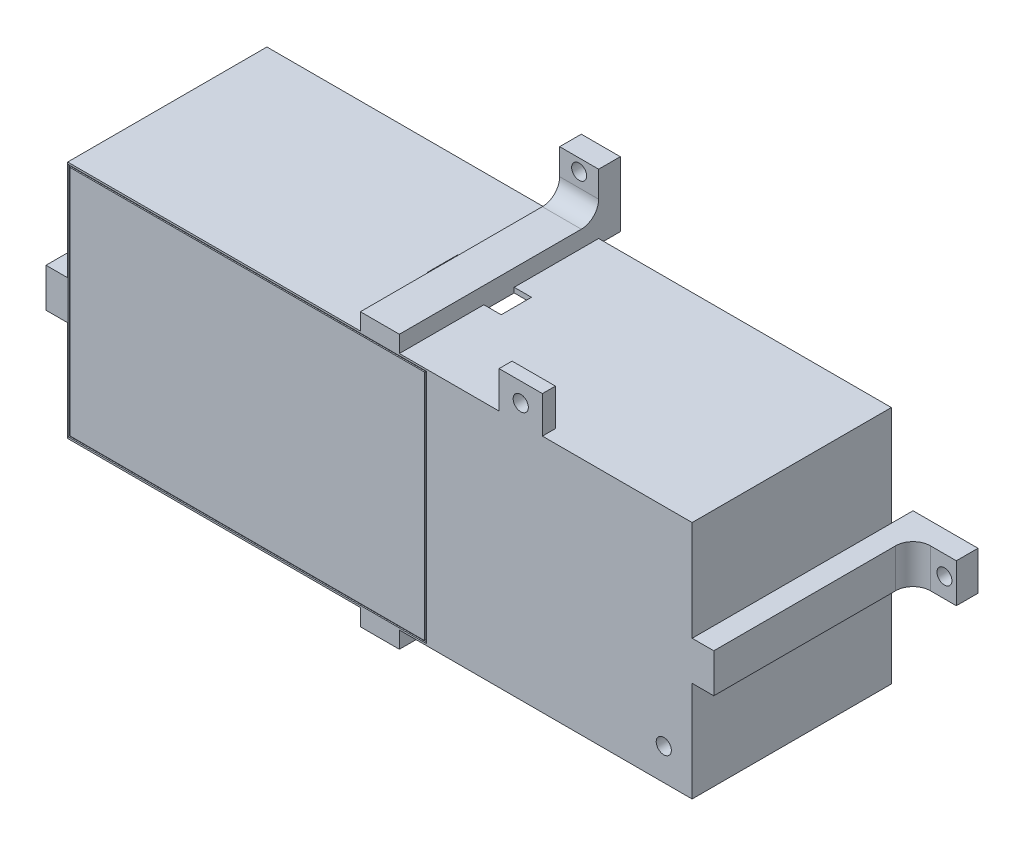
SolidWorks part; units mm, degrees
ref_plane "Front Plane" through (0, 0, 0) normal (0, 0, 1) x (1, 0, 0)
ref_plane "Top Plane" through (0, 0, 0) normal (0, 1, 0) x (1, 0, 0)
ref_plane "Right Plane" through (0, 0, 0) normal (1, 0, 0) x (0, 0, -1)
sketch "Sketch2" plane through (0, 0, 0) normal (0, 0, 1) x (1, 0, 0)
  line L0 (-68.085, -22.5) -> (68.085, 22.5) construction
  line L1 (-68.085, 22.5) -> (68.085, 22.5) construction
  line L2 (-68.085, 22.5) -> (-68.085, -22.5) construction
  line L3 (-68.085, -22.5) -> (68.085, -22.5) construction
  line L4 (68.085, 22.5) -> (68.085, -22.5) construction
  line L5 (-72.085, 26.5) -> (72.085, 26.5) construction
  line L6 (72.085, 26.5) -> (72.085, -26.5) construction
  line L7 (-72.085, -26.5) -> (72.085, -26.5) construction
  line L8 (-72.085, 26.5) -> (-72.085, -26.5) construction
  line L9 (0, 0) -> (-100, 0) construction
  line L10 (-77.085, 4.5) -> (-72.085, 4.5)
  line L11 (-77.085, 4.5) -> (-77.085, -4.5)
  line L12 (-77.085, -4.5) -> (-72.085, -4.5)
  line L13 (-72.085, 4.5) -> (-72.085, -4.5)
  line L14 (-4.5, 31.5) -> (4.5, 31.5)
  line L15 (-4.5, 31.5) -> (-4.5, 26.5)
  line L16 (-4.5, 26.5) -> (4.5, 26.5)
  line L17 (4.5, 31.5) -> (4.5, 26.5)
  line L18 (0, 0) -> (0, 108.7377) construction
  line L19 (-77.085, 4.5) -> (-72.085, -4.5) construction
  line L20 (-4.5, 26.5) -> (4.5, 31.5) construction
  line L21 (77.085, -4.5) -> (72.085, -4.5)
  line L22 (77.085, 4.5) -> (77.085, -4.5)
  line L23 (72.085, 4.5) -> (72.085, -4.5)
  line L24 (77.085, 4.5) -> (72.085, 4.5)
  line L25 (-4.5, -26.5) -> (4.5, -26.5)
  line L26 (-4.5, -31.5) -> (-4.5, -26.5)
  line L27 (-4.5, -31.5) -> (4.5, -31.5)
  line L28 (4.5, -31.5) -> (4.5, -26.5)
  point P4 (0, 0)
  point P23 (-74.585, 0)
  point P25 (0, 29)
  dimension "D1" = 45
  dimension "D2" = 136.17
  dimension "D4" = 5
  dimension "D5" = 9
  dimension "D6" = 5
  dimension "D7" = 9
  dimension "D3" = 4
extrude "Boss-Extrude1" add sketch "Sketch2" along normal blind 48
sketch "Sketch3" plane through (0, 0, 48) normal (0, 0, 1) x (1, 0, 0)
  line L0 (-82.5, 27.64) -> (82.5, -27.64) construction
  line L1 (-82.5, 27.64) -> (82.5, 27.64)
  line L2 (-82.5, 27.64) -> (-82.5, -27.64)
  line L3 (-82.5, -27.64) -> (82.5, -27.64)
  line L4 (82.5, 27.64) -> (82.5, -27.64)
  point P4 (0, 0)
  dimension "D1" = 165
  dimension "D2" = 55.28
extrude "Boss-Extrude2" add sketch "Sketch3" along normal blind 3
sketch "Sketch4" plane through (0, 0, 48) normal (0, 0, 1) x (1, 0, 0)
  line L0 (-4.5, 27.64) -> (4.5, 27.64) construction
  line L1 (4.5, 27.64) -> (4.5, 31.5) construction
  line L2 (4.5, 31.5) -> (-4.5, 31.5) construction
  line L3 (-4.5, 31.5) -> (-4.5, 27.64) construction
  line L4 (4.5, -31.5) -> (4.5, -27.64) construction
  line L5 (4.5, -27.64) -> (-4.5, -27.64) construction
  line L6 (-4.5, -27.64) -> (-4.5, -31.5) construction
  line L7 (-4.5, -31.5) -> (4.5, -31.5) construction
  line L8 (-4.5, 27.64) -> (4.5, 27.64)
  line L9 (4.5, 27.64) -> (4.5, 31.5)
  line L10 (4.5, 31.5) -> (-4.5, 31.5)
  line L11 (-4.5, 31.5) -> (-4.5, 27.64)
  line L12 (4.5, -31.5) -> (4.5, -27.64)
  line L13 (4.5, -27.64) -> (-4.5, -27.64)
  line L14 (-4.5, -27.64) -> (-4.5, -31.5)
  line L15 (-4.5, -31.5) -> (4.5, -31.5)
extrude "Boss-Extrude3" add sketch "Sketch4" along normal up to surface (3 mm away) up to face at (0, 0, 51)
sketch "Sketch5" plane through (0, 4.5, 0) normal (0, 1, 0) x (1, 0, 0)
  line L0 (0, 0) -> (0, -40.7206) construction
  line L1 (-77.085, 0) -> (-87.085, 0)
  line L2 (-77.085, 0) -> (-77.085, -5)
  line L3 (-77.085, -5) -> (-87.085, -5)
  line L4 (-87.085, 0) -> (-87.085, -5)
  line L5 (87.085, 0) -> (87.085, -5)
  line L6 (77.085, 0) -> (87.085, 0)
  line L7 (77.085, 0) -> (77.085, -5)
  line L8 (77.085, -5) -> (87.085, -5)
  dimension "D1" = 5
  dimension "D2" = 10
extrude "Boss-Extrude4" add sketch "Sketch5" against normal up to surface (9 mm away) up to face at (-74.585, -4.5, 24)
sketch "Sketch7" plane through (-4.5, 0, 0) normal (-1, 0, 0) x (0, 0, 1)
  line L0 (0, 0) -> (45.7182, 0) construction
  line L1 (0, 31.5) -> (5, 31.5)
  line L2 (0, 31.5) -> (0, 41.5)
  line L3 (0, 41.5) -> (5, 41.5)
  line L4 (5, 31.5) -> (5, 41.5)
  line L5 (0, -41.5) -> (5, -41.5)
  line L6 (0, -31.5) -> (0, -41.5)
  line L7 (0, -31.5) -> (5, -31.5)
  line L8 (5, -31.5) -> (5, -41.5)
  dimension "D1" = 5
  dimension "D2" = 10
extrude "Boss-Extrude5" add sketch "Sketch7" against normal up to surface (9 mm away) up to face at (4.5, -28.5467, 33)
sketch "Sketch8" plane through (0, 0, 5) normal (0, 0, 1) x (1, 0, 0)
  line L0 (-84.335, 0) -> (-77.085, 0) construction
  line L1 (0, -38.75) -> (0, -31.5) construction
  line L2 (0, 0) -> (0, 49.5906) construction
  line L3 (0, 0) -> (57.6811, 0) construction
  line L4 (4.5, -31.5) -> (-4.5, -31.5) construction
  line L5 (-77.085, -4.5) -> (-77.085, 4.5) construction
  circle A0 centre (-84.335, 0) radius 1.73
  circle A1 centre (0, -38.75) radius 1.73
  circle A2 centre (84.335, 0) radius 1.73
  circle A3 centre (0, 38.75) radius 1.73
  dimension "D1" = 3.46
  dimension "D2" = 3.46
  dimension "D3" = 7.25
  dimension "D4" = 7.25
extrude "Cut-Extrude1" cut sketch "Sketch8" against normal through all
sketch "Metro Express Layout Reference" plane through (0, 0, 51) normal (0, 0, 1) x (1, 0, 0)
  line L0 (0.32, 27.64) -> (0.32, -27.64) construction
  line L1 (14.74, 34.29) -> (68.08, 34.29) construction
  line L2 (14.74, 34.29) -> (14.74, -34.29) construction
  line L3 (14.74, -34.29) -> (68.08, -34.29) construction
  line L4 (68.08, 34.29) -> (68.08, -34.29) construction
  line L5 (82.5, -27.64) -> (82.5, 27.64) construction
  line L7 (-4.5, 27.64) -> (-82.5, 27.64) construction
  line L8 (-82.5, -27.64) -> (-4.5, -27.64) construction
  line L9 (-82.5, 27.64) -> (-82.5, -27.64) construction
  circle A0 centre (32.52, 31.75) radius 1.75 construction
  circle A1 centre (65.54, -20.32) radius 1.75 construction
  point P4 (68.08, 0)
  point P7 (82.5, 0)
  dimension "D5" = 3.5
  dimension "D7" = 3.5
  dimension "D1" = 68.58
  dimension "D2" = 53.34
  dimension "D3" = 17.78
  dimension "D4" = 2.54
  dimension "D6" = 13.97
  dimension "D8" = 2.54
  dimension "D9" = 82.82
  dimension "D10" = 14.42
sketch "Sketch10" plane through (0, 0, 51) normal (0, 0, 1) x (1, 0, 0)
  line L0 (82.5, 27.64) -> (4.5, 27.64) construction
  line L1 (27.52, 27.64) -> (37.52, 27.64)
  line L2 (27.52, 27.64) -> (27.52, 36.14)
  line L3 (27.52, 36.14) -> (37.52, 36.14)
  line L4 (37.52, 27.64) -> (37.52, 36.14)
  line L5 (68.08, 34.29) -> (68.08, -34.29) construction
  line L6 (68.08, -15.32) -> (69.93, -15.32)
  line L7 (68.08, -15.32) -> (68.08, -25.32)
  line L8 (68.08, -25.32) -> (69.93, -25.32)
  line L9 (69.93, -15.32) -> (69.93, -25.32)
  point P6 (32.52, 27.64)
  point P14 (68.08, -20.32)
  dimension "D1" = 8.5
  dimension "D2" = 10
  dimension "D3" = 10
  dimension "D4" = 4.39
extrude "Boss-Extrude6" add sketch "Sketch10" against normal up to surface (3 mm away) up to face at (74.585, 0, 48)
sketch "Sketch11" plane through (0, 0, 51) normal (0, 0, 1) x (1, 0, 0)
  circle A0 centre (32.52, 31.75) radius 1.75
  circle A1 centre (65.54, -20.32) radius 1.75
  circle A2 centre (32.52, 31.75) radius 1.75 construction
  circle A3 centre (65.54, -20.32) radius 1.75 construction
extrude "Cut-Extrude3" cut sketch "Sketch11" against normal through all
sketch "Sketch12" plane through (0, 0, 51) normal (0, 0, 1) x (1, 0, 0)
  line L0 (-82.5, 27.64) -> (-82.5, -27.64) construction
  line L1 (-71.785, 27.03) -> (10.535, 27.03) construction
  line L2 (-71.785, 27.03) -> (-71.785, -27.03) construction
  line L3 (-71.785, -27.03) -> (10.535, -27.03) construction
  line L4 (10.535, 27.03) -> (10.535, -27.03) construction
  line L5 (-71.985, 27.23) -> (-71.985, -27.23)
  line L6 (-12.815, 8.88) -> (12.815, 8.88) construction
  line L7 (-12.815, 8.88) -> (-12.815, -8.88) construction
  line L8 (-12.815, -8.88) -> (12.815, -8.88) construction
  line L9 (12.815, 8.88) -> (12.815, -8.88) construction
  line L10 (-71.985, -27.23) -> (10.735, -27.23)
  line L11 (10.735, 27.23) -> (10.735, -27.23)
  line L12 (-71.985, 27.23) -> (10.735, 27.23)
  line L13 (-71.585, 26.83) -> (-71.585, -26.83)
  line L14 (-71.585, -26.83) -> (10.335, -26.83)
  line L15 (10.335, 26.83) -> (10.335, -26.83)
  line L16 (-71.585, 26.83) -> (10.335, 26.83)
  point P4 (12.815, 0)
  point P5 (-71.785, 0)
  point P8 (-82.5, 0)
  point P15 (0, 8.88)
  dimension "D1" = 82.32
  dimension "D2" = 54.06
  dimension "D3" = 25.63
  dimension "D4" = 17.76
  dimension "D5" = 2.28
  dimension "D6" = 0.2
  dimension "D7" = 0.2
extrude "Cut-Extrude4" cut sketch "Sketch12" against normal blind 0.28
sketch "Sketch13" plane through (0, 0, 48) normal (0, 0, -1) x (-1, 0, 0)
  line L0 (82.5, -27.64) -> (82.5, 27.64)
  line L5 (-82.5, 27.64) -> (-82.5, -27.64)
  line L17 (-82.5, 27.64) -> (-37.52, 27.64) construction
  line L18 (-82.5, -27.64) -> (-72.085, -27.64)
  line L20 (-77.085, -4.5) -> (-72.085, -4.5)
  line L21 (-72.085, -27.64) -> (-72.085, -4.5)
  line L25 (-77.085, -4.5) -> (-77.085, 4.5)
  line L26 (-77.085, 4.5) -> (-72.085, 4.5)
  line L28 (-82.5, 27.64) -> (-72.085, 27.64)
  line L29 (-72.085, 4.5) -> (-72.085, 27.64)
  line L30 (4.5, 27.64) -> (82.5, 27.64) construction
  line L31 (82.5, -27.64) -> (72.085, -27.64)
  line L33 (77.085, -4.5) -> (72.085, -4.5)
  line L34 (72.085, -27.64) -> (72.085, -4.5)
  line L38 (77.085, -4.5) -> (77.085, 4.5)
  line L39 (77.085, 4.5) -> (72.085, 4.5)
  line L41 (82.5, 27.64) -> (72.085, 27.64)
  line L42 (72.085, 4.5) -> (72.085, 27.64)
extrude "Cut-Extrude5" cut sketch "Sketch13" against normal through all
sketch "Sketch14" plane through (0, 0, 48) normal (0, 0, -1) x (-1, 0, 0)
  line L0 (72.085, -4.5) -> (72.085, -27.64) construction
  line L1 (-72.085, 27.64) -> (-37.52, 27.64) construction
  line L2 (-27.52, 27.64) -> (-4.5, 27.64) construction
  line L3 (-72.085, 4.5) -> (-72.085, 27.64) construction
  line L4 (-4.5, -27.64) -> (-72.085, -27.64) construction
  line L6 (72.085, -27.64) -> (4.5, -27.64) construction
  line L10 (72.085, 27.64) -> (72.085, 4.5) construction
  line L11 (4.5, 27.64) -> (72.085, 27.64) construction
  line L15 (-72.085, -27.64) -> (-72.085, -4.5) construction
  line L157 (72.085, -4.5) -> (72.085, 4.5) construction
  line L158 (-72.085, 4.5) -> (-72.085, -4.5) construction
  line L159 (72.085, -27.64) -> (4.5, -27.64)
  line L160 (72.085, -4.5) -> (72.085, -27.64)
  line L161 (72.085, -4.5) -> (72.085, 4.5)
  line L162 (72.085, 27.64) -> (72.085, 4.5)
  line L163 (4.5, 27.64) -> (72.085, 27.64)
  line L164 (-72.085, 4.5) -> (-72.085, -4.5)
  line L165 (-72.085, -27.64) -> (-72.085, -4.5)
  line L166 (-4.5, -27.64) -> (-72.085, -27.64)
  line L167 (-72.085, 4.5) -> (-72.085, 27.64)
  line L168 (-27.52, 27.64) -> (-4.5, 27.64)
  line L169 (-72.085, 27.64) -> (-37.52, 27.64)
  line L170 (-4.5, -26.5) -> (-70.945, -26.5)
  line L171 (-70.945, -26.5) -> (-70.945, -4.5)
  line L172 (-70.945, 4.5) -> (-70.945, -4.5)
  line L173 (-70.945, 4.5) -> (-70.945, 26.5)
  line L174 (-70.945, 26.5) -> (-37.52, 26.5)
  line L175 (-27.52, 26.5) -> (-4.5, 26.5)
  line L176 (4.5, 26.5) -> (70.945, 26.5)
  line L177 (70.945, 26.5) -> (70.945, 4.5)
  line L178 (70.945, -4.5) -> (70.945, 4.5)
  line L179 (70.945, -4.5) -> (70.945, -26.5)
  line L180 (70.945, -26.5) -> (4.5, -26.5)
  line L181 (-37.52, 27.64) -> (-27.52, 27.64)
  line L182 (-37.52, 26.5) -> (-27.52, 26.5)
  line L183 (-4.5, -26.5) -> (-4.5, -27.64)
  line L184 (4.5, -26.5) -> (4.5, -27.64)
  line L185 (-4.5, 27.64) -> (-4.5, 26.5)
  line L186 (4.5, 27.64) -> (4.5, 26.5)
  dimension "D1" = 1.14
extrude "Boss-Extrude7" add sketch "Sketch14" along normal up to surface (43 mm away) up to face at (82.605, 0, 5)
sketch "Sketch15" plane through (0, 0, 5) normal (0, 0, -1) x (-1, 0, 0)
  line L0 (72.085, -17.64) -> (70.945, -17.64)
  line L1 (72.085, -4.5) -> (72.085, -27.64) construction
  line L2 (70.945, -26.5) -> (70.945, 26.5) construction
  line L3 (70.945, -17.64) -> (70.945, -26.5)
  line L4 (4.5, -26.5) -> (70.945, -26.5) construction
  line L5 (70.945, -26.5) -> (62.085, -26.5)
  line L6 (62.085, -26.5) -> (62.085, -27.64)
  line L7 (72.085, -27.64) -> (4.5, -27.64) construction
  line L8 (62.085, -27.64) -> (72.085, -27.64)
  line L9 (72.085, -27.64) -> (72.085, -17.64)
  dimension "D1" = 10
  dimension "D2" = 10
extrude "Cut-Extrude6" cut sketch "Sketch15" against normal blind 33.5
sketch "Sketch16" plane through (0, -27.64, 0) normal (0, -1, 0) x (1, 0, 0)
  line L0 (4.5, 51) -> (4.5, 5) construction
  line L1 (4.5, 38) -> (8.5, 38)
  line L2 (4.5, 38) -> (4.5, 31)
  line L3 (4.5, 31) -> (8.5, 31)
  line L4 (8.5, 38) -> (8.5, 31)
  line L5 (70.945, 48) -> (-70.945, 48) construction
  line L6 (4.5, 17) -> (8.5, 17)
  line L7 (4.5, 17) -> (4.5, 10)
  line L8 (4.5, 10) -> (8.5, 10)
  line L9 (8.5, 17) -> (8.5, 10)
  line L10 (4.5, 5) -> (72.085, 5) construction
  line L11 (0, 0) -> (0, 45.8798) construction
  line L12 (-4.5, 17) -> (-4.5, 10)
  line L13 (-4.5, 10) -> (-8.5, 10)
  line L14 (-8.5, 17) -> (-8.5, 10)
  line L15 (-4.5, 17) -> (-8.5, 17)
  line L16 (-4.5, 31) -> (-8.5, 31)
  line L17 (-4.5, 38) -> (-4.5, 31)
  line L18 (-8.5, 38) -> (-8.5, 31)
  line L19 (-4.5, 38) -> (-8.5, 38)
  dimension "D1" = 7
  dimension "D2" = 7
  dimension "D3" = 4
  dimension "D4" = 4
  dimension "D5" = 10
  dimension "D6" = 5
extrude "Cut-Extrude7" cut sketch "Sketch16" against normal up to surface (1.14 mm away) up to face at (-12.417, -26.5, 19.3)
sketch "Sketch17" plane through (0, 27.64, 0) normal (0, 1, 0) x (1, 0, 0)
  line L0 (4.5, -51) -> (4.5, -5) construction
  line L1 (4.5, -24.5) -> (8.5, -24.5)
  line L2 (4.5, -24.5) -> (4.5, -31.5)
  line L3 (4.5, -31.5) -> (8.5, -31.5)
  line L4 (8.5, -24.5) -> (8.5, -31.5)
  line L5 (0, 0) -> (0, -41.863) construction
  line L6 (4.5, 0) -> (-4.5, 0) construction
  line L7 (72.085, -28) -> (24.4078, -28) construction
  line L8 (72.085, -51) -> (72.085, -5) construction
  line L9 (-4.5, -24.5) -> (-4.5, -31.5)
  line L10 (-4.5, -31.5) -> (-8.5, -31.5)
  line L11 (-8.5, -24.5) -> (-8.5, -31.5)
  line L12 (-4.5, -24.5) -> (-8.5, -24.5)
  point P14 (8.5, -28)
  dimension "D1" = 7
  dimension "D2" = 4
extrude "Cut-Extrude8" cut sketch "Sketch17" against normal up to surface (1.14 mm away) up to face at (0, 26.5, 14.5)
fillet "Fillet1" radius 4 4 edges at (-77.085, 0, 5) (0, 31.5, 5) (77.085, 0, 5) (0, -31.5, 5)
sketch "Sketch18" plane through (0, 0, 5) normal (0, 0, -1) x (-1, 0, 0)
  line L6 (72.085, -27.64) -> (72.085, -17.64)
  line L7 (72.085, -17.64) -> (70.945, -17.64)
  line L8 (70.945, -17.64) -> (70.945, -26.5)
  line L9 (70.945, -26.5) -> (62.085, -26.5)
  line L10 (62.085, -26.5) -> (62.085, -27.64)
  line L11 (62.085, -27.64) -> (72.085, -27.64)
  line L12 (72.085, -27.64) -> (72.085, -17.64)
  line L13 (72.085, -17.64) -> (70.945, -17.64)
  line L14 (70.945, -17.64) -> (70.945, -26.5)
  line L15 (70.945, -26.5) -> (62.085, -26.5)
  line L16 (62.085, -26.5) -> (62.085, -27.64)
  line L17 (62.085, -27.64) -> (72.085, -27.64)
  dimension "D1" = 0
extrude "Boss-Extrude8" add sketch "Sketch18" against normal blind 6
